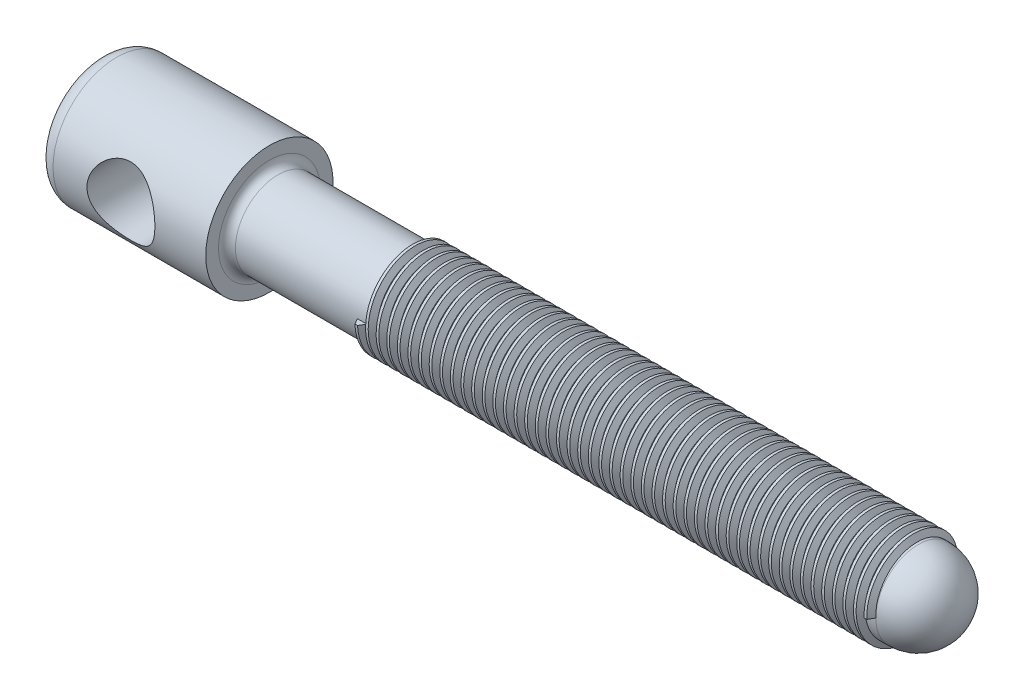
SolidWorks part; units mm, degrees
ref_plane "Front Plane" through (0, 0, 0) normal (0, 0, 1) x (1, 0, 0)
ref_plane "Top Plane" through (0, 0, 0) normal (0, 1, 0) x (1, 0, 0)
ref_plane "Right Plane" through (0, 0, 0) normal (1, 0, 0) x (0, 0, -1)
sketch "Sketch1" plane through (0, 0, 0) normal (0, 0, 1) x (1, 0, 0)
  line L0 (0, 0) -> (14380.252, 0) construction
  line L1 (0, 0) -> (0, -14380.252) construction
  line L2 (0, 0) -> (0, 5.5)
  line L3 (2, 7.5) -> (20, 7.5)
  line L4 (20, 7.5) -> (20, 6)
  line L5 (21, 5) -> (96.4645, 5)
  line L6 (0, 0) -> (101.4645, 0)
  arc A0 (0, 5.5) -> (2, 7.5) centre (2, 5.5) cw
  arc A1 (20, 6) -> (21, 5) centre (21, 6) ccw
  arc A2 (96.4645, 5) -> (101.4645, 0) centre (96.4645, 0) cw
  point P14 (42.5795, 0)
  point P16 (0, 0)
  point P17 (100, 3.5355)
  point P19 (0, 0)
  dimension "D1" = 5
  dimension "D2" = 2
  dimension "D5" = 1
  dimension "D3" = 15
  dimension "D4" = 20
  dimension "D6" = 80
revolve "Revolve1" add sketch "Sketch1" angle 360 about L6
sketch "Sketch2" plane through (0, 0, 0) normal (0, 0, 1) x (1, 0, 0)
  circle A0 centre (10, 0) radius 4
  dimension "D1" = 10
  dimension "D2" = 8
extrude "Cut-Extrude1" cut sketch "Sketch2" against normal through all both and the other way through all
thread "Thread1" pitch 1.25 method extrude profile "Thread Profile1" start angle 0, offset 0, length 60, pitch 1.25, diameter 10
ref_plane "Plane1" through (96.4645, 0, 5) normal (0, 1, 0) x (0, 0, -1)
sketch "Thread Profile1" plane through (96.4645, 0, 5) normal (0, 1, 0) x (0, 0, -1)
  line L0 (0, 0) -> (0, 1.25) construction
  line L11 (0, 0) -> (0, 1.0937)
  line L12 (0, 1.0937) -> (-0.6766, 0.7031)
  line L13 (-0.6766, 0.7031) -> (-0.6766, 0.3906)
  line L15 (-0.6766, 0.3906) -> (0, 0)
  line L17 (-0.6766, 0.5469) -> (0, 0.5469) construction
  point P2 (0, 0)
  dimension "Pitch" = 1.25
  dimension "Profile_Angle" = 60
  dimension "Profile_Land" = 0.3125
  dimension "Profile_Height" = 0.6766
